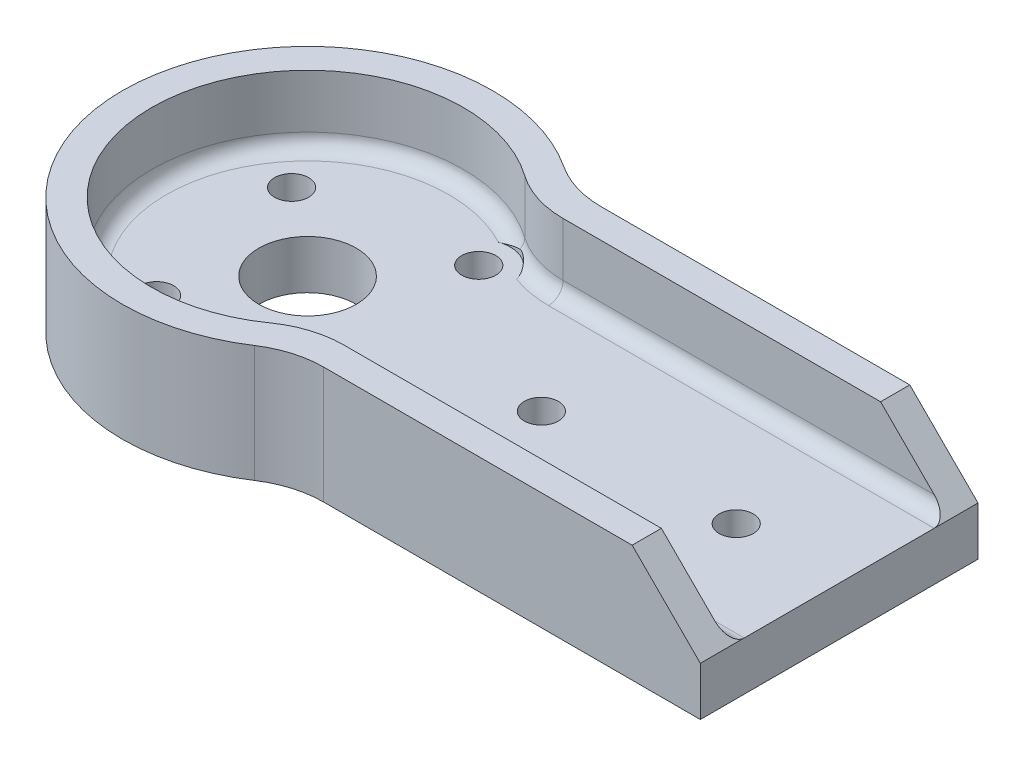
SolidWorks part; units mm, degrees
ref_plane "Front Plane" through (0, 0, 0) normal (0, 0, 1) x (1, 0, 0)
ref_plane "Top Plane" through (0, 0, 0) normal (0, 1, 0) x (1, 0, 0)
ref_plane "Right Plane" through (0, 0, 0) normal (1, 0, 0) x (0, 0, -1)
sketch "Sketch1" plane through (0, 0, 0) normal (0, 1, 0) x (1, 0, 0)
  line L1 (12.5673, 14.25) -> (54.5673, 14.25)
  line L3 (12.5673, -14.25) -> (54.5673, -14.25)
  line L4 (54.5673, 14.25) -> (54.5673, -14.25)
  arc A0 (12.5673, 14.25) -> (12.5673, -14.25) centre (0, 0) ccw
  dimension "D1" = 38
  dimension "D2" = 42
extrude "Boss-Extrude1" add sketch "Sketch1" along normal blind 5
sketch "Sketch2" plane through (0, 5, 0) normal (0, 1, 0) x (1, 0, 0)
  circle A0 centre (0, 0) radius 5
  dimension "D1" = 10
extrude "Cut-Extrude1" cut sketch "Sketch2" against normal blind 5
sketch "Sketch3" plane through (0, 5, 0) normal (0, 1, 0) x (1, 0, 0)
  line L0 (12.5673, -14.25) -> (54.5673, -14.25) construction
  circle A0 centre (7.8222, 9.75) radius 1.75
  circle A1 centre (0, 0) radius 5 construction
  circle A2 centre (10.5, -6.7823) radius 1.75
  circle A3 centre (-6.0323, -9.4601) radius 1.75
  circle A4 centre (-8.7101, 7.0722) radius 1.75
  point P15 (0.895, 0.145)
  dimension "D1" = 3.5
  dimension "D2" = 12.5
  dimension "D3" = 24
  dimension "D4" = 4
extrude "Cut-Extrude2" cut sketch "Sketch3" against normal up to vertex (5 mm away) up to point (0, 0, 0)
sketch "Sketch4" plane through (0, 5, 0) normal (0, 1, 0) x (1, 0, 0)
  circle A0 centre (24, 0) radius 1.75
  circle A1 centre (44, 0) radius 1.75
  circle A2 centre (0, 0) radius 5 construction
  dimension "D1" = 3.5
  dimension "D2" = 3.5
  dimension "D3" = 24
  dimension "D4" = 20
extrude "Cut-Extrude3" cut sketch "Sketch4" against normal blind 5
sketch "Sketch5" plane through (0, 5, 0) normal (0, 1, 0) x (1, 0, 0)
  line L1 (54.5673, 14.25) -> (12.5673, 14.25)
  line L2 (54.5673, 14.25) -> (54.5673, 11.25)
  line L3 (54.5673, 11.25) -> (11.3771, 11.25)
  line L5 (54.5673, -14.25) -> (12.5673, -14.25)
  line L6 (54.5673, -14.25) -> (54.5673, -11.25)
  line L7 (54.5673, -11.25) -> (11.3771, -11.25)
  arc A0 (12.5673, 14.25) -> (12.5673, -14.25) centre (0, 0) ccw
  arc A1 (11.3771, 11.25) -> (11.3771, -11.25) centre (0, 0) ccw
  arc A2 (12.5673, 14.25) -> (12.5673, -14.25) centre (0, 0) ccw construction
  dimension "D1" = 3
  dimension "D3" = 3
  dimension "D4" = 0
  dimension "D2" = 3
extrude "Boss-Extrude2" add sketch "Sketch5" along normal blind 7
fillet "Fillet1" radius 10 2 edges at (12.5673, 6, -14.25) (12.5673, 6, 14.25)
fillet "Fillet2" radius 10 2 edges at (11.3771, 8.5, -11.25) (11.3771, 8.5, 11.25)
fillet "Fillet3" radius 1.5 5 edges at (34.7743, 5, 11.25) (11.9589, 5, 11.7177) (34.7743, 5, -11.25) (11.9589, 5, -11.7177) (-16, 5, 0)
sketch "Sketch6" plane through (0, 5, 0) normal (0, 1, 0) x (1, 0, 0)
  circle A0 centre (-8.7101, 7.0722) radius 3.25
  circle A1 centre (7.8222, 9.75) radius 3.25
  circle A2 centre (10.5, -6.7823) radius 3.25
  circle A3 centre (-6.0323, -9.4601) radius 3.25
  dimension "D1" = 6.5
  dimension "D2" = 6.5
  dimension "D3" = 6.5
  dimension "D4" = 6.5
extrude "Cut-Extrude4" cut sketch "Sketch6" along normal blind 10
chamfer "Chamfer1" distance 7 angle 45 2 edges at (54.5673, 12, 12.75) (54.5673, 12, -12.75)
